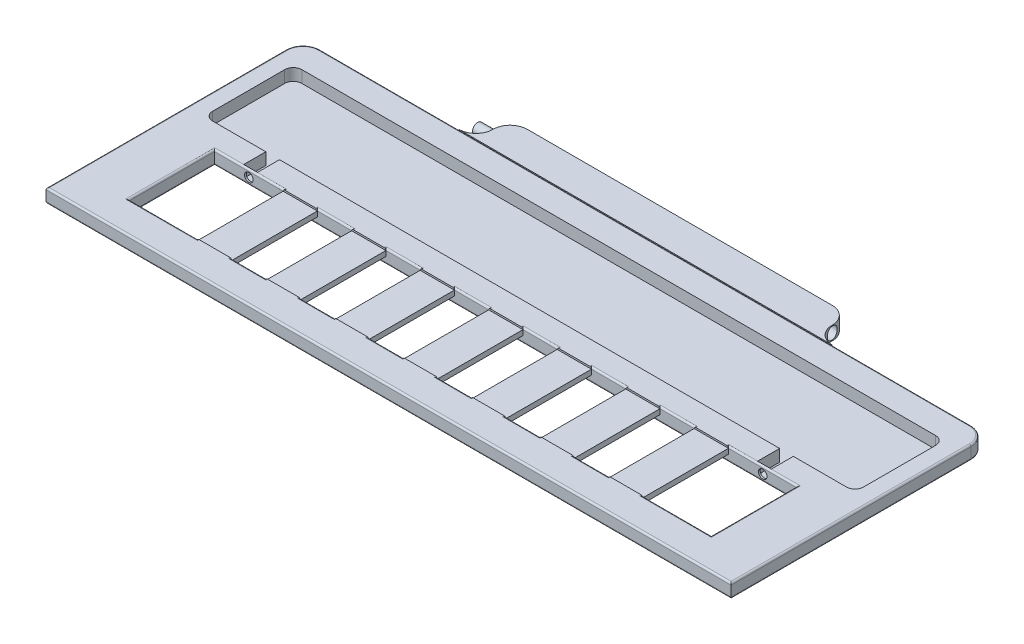
SolidWorks part; units mm, degrees
ref_plane "Plano frontal" through (0, 0, 0) normal (0, 0, 1) x (1, 0, 0)
ref_plane "Plano superior" through (0, 0, 0) normal (0, 1, 0) x (1, 0, 0)
ref_plane "Plano direito" through (0, 0, 0) normal (1, 0, 0) x (0, 0, -1)
sketch "Esboço1" plane through (0, 0, 0) normal (0, 1, 0) x (1, 0, 0)
  line L1 (200, -75) -> (-200, -75)
  line L2 (200, -75) -> (200, 75)
  line L3 (200, 75) -> (-200, 75)
  line L4 (-200, -75) -> (-200, 75)
  line L5 (200, -75) -> (-200, 75) construction
  line L6 (200, 75) -> (-200, -75) construction
  point P0 (0, 0)
  dimension "D1" = 150
  dimension "D2" = 400
extrude "Ressalto-extrusão1" add sketch "Esboço1" along normal blind 8
sketch "Esboço2" plane through (0, 8, 0) normal (0, 1, 0) x (1, 0, 0)
  line L0 (-200, 75) -> (-200, -75) construction
  line L1 (170, -56.5653) -> (-170, -56.5653)
  line L2 (170, -56.5653) -> (170, -6.5653)
  line L3 (170, -6.5653) -> (-170, -6.5653)
  line L4 (-170, -56.5653) -> (-170, -6.5653)
  line L5 (170, -56.5653) -> (-170, -6.5653) construction
  line L6 (170, -6.5653) -> (-170, -56.5653) construction
  line L7 (200, -75) -> (200, 75) construction
  point P0 (0, -31.5653)
  dimension "D1" = 50
  dimension "D2" = 30
  dimension "D3" = 30
extrude "Corte-extrusão1" cut sketch "Esboço2" against normal blind 8
sketch "Esboço8" plane through (0, 0, 6.5653) normal (0, 0, 1) x (1, 0, 0)
  line L0 (-200, 8) -> (200, 8) construction
  line L1 (-130, 8) -> (-110, 8)
  line L2 (-130, 8) -> (-130, 4)
  line L3 (-130, 4) -> (-110, 4)
  line L4 (-110, 8) -> (-110, 4)
  line L5 (170, 8) -> (-170, 8) construction
  line L6 (-170, 0) -> (-170, 8) construction
  dimension "D1" = 4
  dimension "D2" = 20
  dimension "D3" = 40
extrude "Ressalto-extrusão4" add sketch "Esboço8" along normal up to vertex (50 mm away) up to point (-170, 8, 56.5653)
pattern_linear "Padrão linear1" count 7 spacing 40 along (1, 0, 0) of "Ressalto-extrusão4"
sketch "Esboço9" plane through (0, 4, 0) normal (0, -1, 0) x (1, 0, 0)
  line L0 (-170, 56.5653) -> (170, 56.5653) construction
  line L1 (-110, 56.5653) -> (-110, 6.5653) construction
  line L4 (-130, 6.5653) -> (-110, 6.5653) construction
  circle A0 centre (-120, 46.5653) radius 4
  circle A1 centre (-120, 16.5653) radius 4
  dimension "D2" = 8
  dimension "D4" = 8
  dimension "D1" = 10
  dimension "D3" = 10
  dimension "D5" = 10
  dimension "D6" = 10
extrude "Corte-extrusão4" cut sketch "Esboço9" against normal blind 2
pattern_linear "Padrão linear2" count 7 spacing 40 along (1, 0, 0) of "Corte-extrusão4"
sketch "Esboço10" plane through (0, 0, 6.5653) normal (0, 0, 1) x (1, 0, 0)
  line L0 (-150, 8) -> (-150, 0) construction
  line L1 (-130, 8) -> (-170, 8) construction
  line L2 (170, 0) -> (-170, 0) construction
  line L4 (0, 0) -> (0, 39.8568) construction
  circle A0 centre (-150, 4) radius 2.5
  circle A1 centre (150, 4) radius 2.5
  dimension "D1" = 5
extrude "Corte-extrusão5" cut sketch "Esboço10" against normal blind 10
sketch "Esboço11" plane through (0, 8, 0) normal (0, 1, 0) x (1, 0, 0)
  line L0 (-170, -31.5653) -> (170, -31.5653) construction
  line L1 (-170, -6.5653) -> (-170, -56.5653) construction
  line L2 (170, -56.5653) -> (170, -6.5653) construction
ref_plane "Plano1" through (0, 0, 31.5653) normal (0, 0, 1) x (1, 0, 0)
mirror "Espelhar1" about plane through (0, 0, 31.5653) normal (0, 0, 1) of "Corte-extrusão5"
fillet "Filete2" radius 1 44 edges at (170, 0, 31.5653) (0, 0, 56.5653) (-170, 0, 31.5653) (0, 0, 6.5653) (-200, 0, 0) (0, 0, 75) (200, 0, 0) (0, 0, -75) (170, 8, 31.5653) (150, 8, 6.5653) (130, 8, 31.5653) (150, 8, 56.5653) (0, 8, -75) (200, 8, 0) (0, 8, 75) (-200, 8, 0) (-170, 8, 31.5653) (-150, 8, 56.5653) (-130, 8, 31.5653) (-150, 8, 6.5653) (-100, 8, 6.5653) (-110, 8, 31.5653) (-100, 8, 56.5653) (-90, 8, 31.5653) (-60, 8, 6.5653) (-70, 8, 31.5653) (-60, 8, 56.5653) (-50, 8, 31.5653) (-20, 8, 6.5653) (-30, 8, 31.5653) (-20, 8, 56.5653) (-10, 8, 31.5653) (20, 8, 6.5653) (10, 8, 31.5653) (20, 8, 56.5653) (30, 8, 31.5653) (60, 8, 6.5653) (50, 8, 31.5653) (60, 8, 56.5653) (70, 8, 31.5653) (100, 8, 6.5653) (90, 8, 31.5653) (100, 8, 56.5653) (110, 8, 31.5653)
sketch "Esboço12" plane through (0, 8, 0) normal (0, 1, 0) x (1, 0, 0)
  line L0 (-150, -5.5653) -> (-150, -57.5653) construction
  line L1 (-154, 7.4347) -> (-146, 7.4347)
  line L2 (-154, 7.4347) -> (-154, -5.5653)
  line L3 (-154, -5.5653) -> (-146, -5.5653)
  line L4 (-146, 7.4347) -> (-146, -5.5653)
  line L6 (-129, -57.5653) -> (-171, -57.5653) construction
  line L8 (-171, -5.5653) -> (-129, -5.5653) construction
  dimension "D1" = 8
  dimension "D2" = 13
sketch "Esboço13" plane through (0, 0, 6.5653) normal (0, 0, 1) x (1, 0, 0)
  line L0 (-150, 6.5) -> (-150, 1.5) construction
  circle A0 centre (-150, 4) radius 2.5 construction
extrude "Corte-extrusão6" cut sketch "Esboço12" against normal blind 7
sketch "Esboço14" plane through (0, 8, 0) normal (0, 1, 0) x (1, 0, 0)
  line L0 (0, 74) -> (0, -74) construction
  line L2 (-199, -74) -> (199, -74) construction
  line L3 (199, 74) -> (-199, 74) construction
ref_plane "Plano2" through (0, 0, 0) normal (-1, 0, 0) x (0, 0, 1)
mirror "Espelhar2" about plane through (0, 0, 0) normal (-1, 0, 0) of "Corte-extrusão6"
sketch "Esboço15" plane through (0, 0, -75) normal (0, 0, -1) x (-1, 0, 0)
  line L0 (-199, 8) -> (199, 8) construction
  line L1 (99, 0) -> (-99, 0)
  line L2 (99, 0) -> (99, 8)
  line L3 (99, 8) -> (-99, 8)
  line L4 (-99, 0) -> (-99, 8)
  line L5 (99, 0) -> (-99, 8) construction
  line L6 (99, 8) -> (-99, 0) construction
  point P0 (0, 4)
  dimension "D1" = 198
extrude "Ressalto-extrusão5" add sketch "Esboço15" along normal blind 20
sketch "Esboço17" plane through (99, 0, 0) normal (1, 0, 0) x (0, 0, -1)
  circle A0 centre (85, 4) radius 3.5
  dimension "D1" = 7
extrude "Corte-extrusão7" cut sketch "Esboço17" against normal blind 10
sketch "Esboço18" plane through (-99, 0, 0) normal (-1, 0, 0) x (0, 0, 1)
  circle A0 centre (-85, 4) radius 3
  dimension "D1" = 6
extrude "Ressalto-extrusão6" add sketch "Esboço18" along normal blind 9
fillet "Filete3" radius 10 10 edges at (199.7071, 0.2929, -74.7071) (199.7071, 7.7071, -74.7071) (-199.7071, 0.2929, -74.7071) (-199.7071, 7.7071, -74.7071) (-200, 4, -75) (-99, 4, -75) (200, 4, -75) (99, 4, -75) (-99, 4, -95) (99, 4, -95)
sketch "Esboço19" plane through (0, 8, 0) normal (0, 1, 0) x (1, 0, 0)
  line L1 (-185, 59.3795) -> (185, 59.3795)
  line L2 (-190, 54.3795) -> (-190, 12.3141)
  line L3 (-185, 7.3141) -> (185, 7.3141)
  line L4 (190, 54.3795) -> (190, 12.3141)
  arc A0 (185, 7.3141) -> (190, 12.3141) centre (185, 12.3141) ccw
  arc A1 (185, 59.3795) -> (190, 54.3795) centre (185, 54.3795) cw
  arc A2 (-190, 12.3141) -> (-185, 7.3141) centre (-185, 12.3141) ccw
  arc A3 (-185, 59.3795) -> (-190, 54.3795) centre (-185, 54.3795) ccw
  dimension "D1" = 5
extrude "Corte-extrusão8" cut sketch "Esboço19" against normal up to surface (7 mm away) up to face at (-150, 1, -0.9347)
sketch "Esboço20" plane through (0, 8, 0) normal (0, 1, 0) x (1, 0, 0)
  line L1 (-170, -6.5653) -> (170, -6.5653)
  line L2 (-170, -6.5653) -> (-170, -56.5653)
  line L3 (-170, -56.5653) -> (170, -56.5653)
  line L4 (170, -6.5653) -> (170, -56.5653)
extrude "Corte-extrusão9" cut sketch "Esboço20" against normal blind 1
